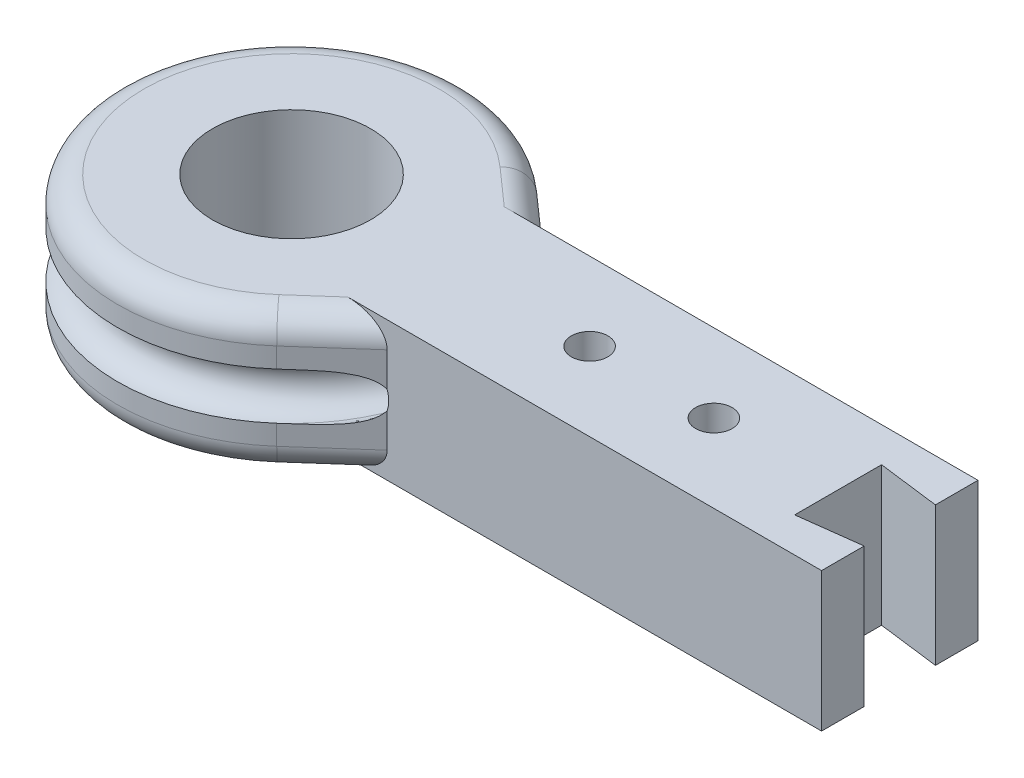
SolidWorks part; units mm, degrees
ref_plane "Front Plane" through (0, 0, 0) normal (0, 0, 1) x (1, 0, 0)
ref_plane "Top Plane" through (0, 0, 0) normal (0, 1, 0) x (1, 0, 0)
ref_plane "Right Plane" through (0, 0, 0) normal (1, 0, 0) x (0, 0, -1)
sketch "Sketch1" plane through (0, 0, 0) normal (0, 1, 0) x (1, 0, 0)
  line L0 (-12.4221, 0) -> (31.45, 0) construction
  line L1 (0, 8.1775) -> (0, -7.8417) construction
  line L2 (10, 4.5) -> (6.632, 7.4844)
  line L3 (10, -4.5) -> (35, -4.5)
  line L5 (10, 4.5) -> (35, 4.5)
  line L6 (35, -4.5) -> (35, -2.05)
  line L7 (10, -4.5) -> (35, 4.5) construction
  line L8 (10, 4.5) -> (35, -4.5) construction
  line L9 (10, -4.5) -> (6.632, -7.4844)
  line L10 (10, 4.5) -> (10, -4.5) construction
  line L21 (35, 2.05) -> (31.45, 2.5)
  line L23 (31.45, -2.5) -> (31.45, 2.5)
  line L26 (31.45, -2.5) -> (31.2787, -3.1603) construction
  line L27 (31.45, 2.5) -> (32.1221, 3.464) construction
  line L28 (35, -2.05) -> (31.45, -2.5)
  line L30 (35, 2.05) -> (35, 4.5)
  arc A0 (6.632, 7.4844) -> (6.632, -7.4844) centre (0, 0) ccw
  circle A1 centre (0, 0) radius 4.55
  point P7 (22.5, 0)
  point P20 (-4.55, 0)
  point P44 (35, 2.05)
  point P48 (35, -2.05)
  dimension "D1" = 20
  dimension "D4" = 9.1
  dimension "D9" = 3.55
  dimension "D2" = 25
  dimension "D3" = 9
  dimension "D6" = 2
  dimension "D10" = 2
  dimension "D14" = 2.45
extrude "Boss-Extrude2" add sketch "Sketch1" along normal blind 8 contours A1 | L3 L6 L28 L23 L21 L30 L5 L2 A0 L9 region at (0, 0, 0)
sketch "Sketch4" plane through (-6.6668, 16.5353, 0) normal (0, 0, 1) x (0, 1, 0)
  line L2 (-8.5353, -13.2988) -> (-8.5353, 3.3332) construction
  line L3 (-8.5353, 3.3332) -> (-16.5353, 3.3332) construction
  line L8 (-16.5353, -6.6668) -> (-4.9826, -6.6668) construction
  arc A1 (-13.8853, 3.3332) -> (-11.1853, 3.3332) centre (-12.5353, 3.3332) ccw
  ellipse E0 centre (-12.5353, 3.3332) end of major axis (-13.8853, 3.3332) minor radius 1.05 (-11.1853, 3.3332) -> (-13.8853, 3.3332) ccw
  point P0 (-12.5353, 3.3332)
  point P1 (-12.5353, 3.3332)
  point P13 (-8.5353, 3.3019)
  point P22 (-12.5353, 3.3332)
  dimension "D1" = 2.7
  dimension "D2" = 1.05
fillet "Fillet2" radius 1.5 6 edges at (8.316, 0, -5.9922) (8.316, 0, 5.9922) (8.316, 8, -5.9922) (8.316, 8, 5.9922) (-10, 0, 0) (-10, 8, 0)
sketch "Sketch5" plane through (0, 8, 0) normal (0, 1, 0) x (1, 0, 0)
  line L0 (10, 6.5426) -> (10, -6.3371) construction
  line L1 (31.45, 7.6045) -> (31.45, -7.4675) construction
  line L2 (0, 0) -> (39.1502, 0) construction
  circle A0 centre (17.15, 0) radius 1.05
  circle A1 centre (24.3, 0) radius 1.05
  point P0 (10, -4.5)
  point P1 (10, 4.5)
  point P16 (31.45, 0.0685)
  dimension "D2" = 2.1
  dimension "D1" = 7.15
  dimension "D3" = 7.15
extrude "Cut-Extrude1" cut sketch "Sketch5" against normal blind 10 contours A1 | A0
revolve "Cut-Revolve1" cut sketch "Sketch4" angle 360 about L8
